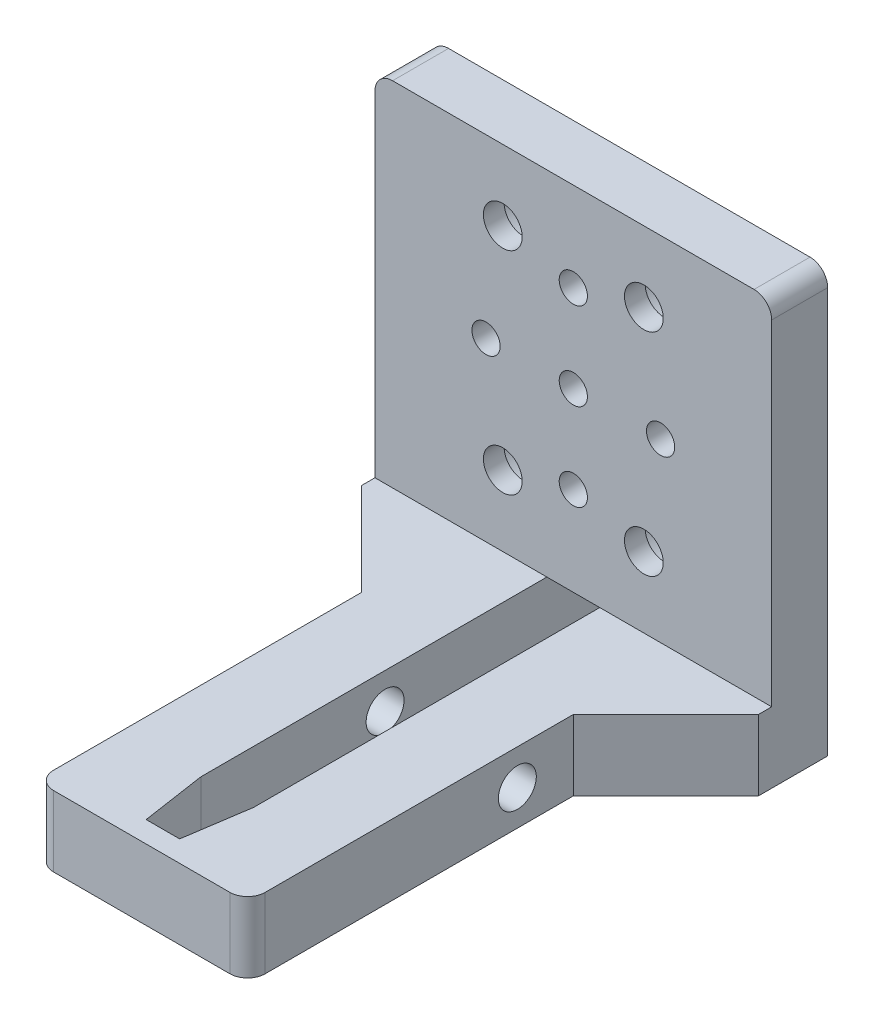
SolidWorks part; units mm, degrees
ref_plane "Front Plane" through (0, 0, 0) normal (0, 0, 1) x (1, 0, 0)
ref_plane "Top Plane" through (0, 0, 0) normal (0, 1, 0) x (1, 0, 0)
ref_plane "Right Plane" through (0, 0, 0) normal (1, 0, 0) x (0, 0, -1)
sketch "Sketch1" plane through (0, 0, 0) normal (0, 0, 1) x (1, 0, 0)
  line L1 (-11.25, 10) -> (11.25, 10)
  line L2 (-11.25, 10) -> (-11.25, -10)
  line L3 (-11.25, -10) -> (11.25, -10)
  line L4 (11.25, 10) -> (11.25, -10)
  line L5 (0, -10) -> (0, 10) construction
  line L6 (-11.25, 0) -> (11.25, 0) construction
  point P0 (0, 0)
  dimension "D1" = 20
  dimension "D2" = 22.5
extrude "Boss-Extrude1" add sketch "Sketch1" along normal blind 3.175
hole_wizard "Tap Drill for M2x0.4 Tap2" positions "Sketch7" profile "Sketch8" hole size "M2x0.4" standard "ANSI Metric" end condition through all
sketch "Sketch7" plane through (0, 0, 3.175) normal (0, 0, 1) x (1, 0, 0)
  line L2 (-4.9497, 0) -> (0, -4.9497)
  line L3 (-4.9497, 0) -> (0, 4.9497)
  line L4 (0, -4.9497) -> (4.9497, 0)
  line L5 (0, 4.9497) -> (4.9497, 0)
  line L6 (2.4749, -2.4749) -> (-2.4749, 2.4749) construction
  line L7 (-2.4749, -2.4749) -> (2.4749, 2.4749) construction
  line L8 (11.25, 10) -> (-11.25, 10) construction
  point P810 (0, 0)
  point P1137 (-4.9497, 0)
  point P1138 (0, -4.9497)
  point P1139 (4.9497, 0)
  point P1140 (0, 4.9497)
  dimension "D1" = 7
  dimension "D2" = 45
sketch "Sketch8" plane through (0, 0, 3.175) normal (1, 0, 0) x (0, -1, 0)
  line L0 (0, 0) -> (0, 3.175)
  line L1 (0, 3.175) -> (0.8, 3.175)
  line L2 (0.8, 3.175) -> (0.8, 0)
  line L5 (0.8, 0) -> (0, 0)
  line L11 (0, -6.35) -> (0, 107.95) construction
  dimension "Thru Hole Dia." = 1.6
  dimension "Thru Hole Depth" = 3.175
sketch "Sketch10" plane through (0, -10, 0) normal (0, -1, 0) x (1, 0, 0)
  line L0 (-11.25, 0) -> (11.25, 0) construction
  line L1 (0, 0) -> (0, 27.65) construction
  line L2 (6, 27.65) -> (-6, 27.65)
  line L3 (-6, 27.65) -> (-6, 3.175)
  line L4 (-11.25, 3.175) -> (-11.25, 0)
  line L5 (-11.25, 0) -> (-1.5, 0)
  line L6 (-0.95, 26.45) -> (-1.5, 22.8)
  line L7 (-0.95, 26.45) -> (0.95, 26.45)
  line L8 (-1.5, 22.8) -> (-1.5, 0)
  line L9 (-6, 3.175) -> (-11.25, 3.175)
  line L10 (11.25, 0) -> (1.5, 0)
  line L11 (11.25, 3.175) -> (11.25, 0)
  line L12 (6, 3.175) -> (11.25, 3.175)
  line L13 (1.5, 22.8) -> (1.5, 0)
  line L14 (6, 27.65) -> (6, 3.175)
  line L15 (0.95, 26.45) -> (1.5, 22.8)
  point P4 (0, 0)
  point P9 (0, 27.65)
  point P20 (0, 26.45)
  dimension "D1" = 22.5
  dimension "D2" = 27.65
  dimension "D3" = 6
  dimension "D4" = 0.95
  dimension "D5" = 26.45
  dimension "D6" = 1.5
  dimension "D7" = 22.8
  dimension "D8" = 3.175
extrude "Boss-Extrude2" add sketch "Sketch10" along normal blind 4
chamfer "Chamfer1" distance 6 angle 45 2 edges at (-6, -12, 3.175) (6, -12, 3.175)
hole_wizard "M2 Clearance Hole1" positions "Sketch14" profile "Sketch13" hole size "M2" standard "ANSI Metric" end condition through all
sketch "Sketch14" plane through (-11.25, 0, 0) normal (-1, 0, 0) x (0, 0, 1)
  line L0 (12.35, -12) -> (27.65, -12) construction
  line L1 (27.65, -14) -> (27.65, -10) construction
  point P0 (12.35, -12)
  dimension "D1" = 15.3
sketch "Sketch13" plane through (-11.25, -12, 12.35) normal (0, 1, 0) x (0, 0, 1)
  line L0 (0, 0) -> (0, 22.5)
  line L1 (0, 22.5) -> (1.075, 22.5)
  line L2 (1.075, 22.5) -> (1.075, 0)
  line L5 (1.075, 0) -> (0, 0)
  line L11 (0, -6.35) -> (0, 107.95) construction
  dimension "Thru Hole Dia." = 2.15
  dimension "Thru Hole Depth" = 22.5
fillet "Fillet1" radius 1 4 edges at (-11.25, 10, 1.5875) (11.25, 10, 1.5875) (-6, -12, 27.65) (6, -12, 27.65)
hole_wizard "CBORE for M2 SHCS1" positions "Sketch15" profile "Sketch16" counterbore size "M2" standard "ANSI Metric" end condition through all
sketch "Sketch15" plane through (0, 0, 0) normal (0, 0, -1) x (-1, 0, 0)
  line L1 (-4, 6) -> (4, 6)
  line L2 (-4, 6) -> (-4, -6)
  line L3 (-4, -6) -> (4, -6)
  line L4 (4, 6) -> (4, -6)
  line L5 (-4, 6) -> (4, -6) construction
  line L6 (-4, -6) -> (4, 6) construction
  point P1 (4, -6)
  point P106 (-4, 6)
  point P107 (-4, -6)
  point P108 (4, 6)
  dimension "D1" = 8
  dimension "D2" = 12
sketch "Sketch16" plane through (-4, -6, 0) normal (1, 0, 0) x (0, 1, 0)
  line L0 (0, 0) -> (0, 27.65)
  line L1 (0, 27.65) -> (1.1, 27.65)
  line L3 (1.1, 27.65) -> (1.1, 2)
  line L4 (1.1, 2) -> (2.2, 2)
  line L5 (2.2, 2) -> (2.2, 0)
  line L7 (2.2, 0) -> (0, 0)
  line L11 (0, -6.35) -> (0, 107.95) construction
  dimension "Thru Hole Dia." = 2.2
  dimension "Thru Hole Depth" = 27.65
  dimension "C'Bore Dia." = 4.4
  dimension "C'Bore Depth" = 2
